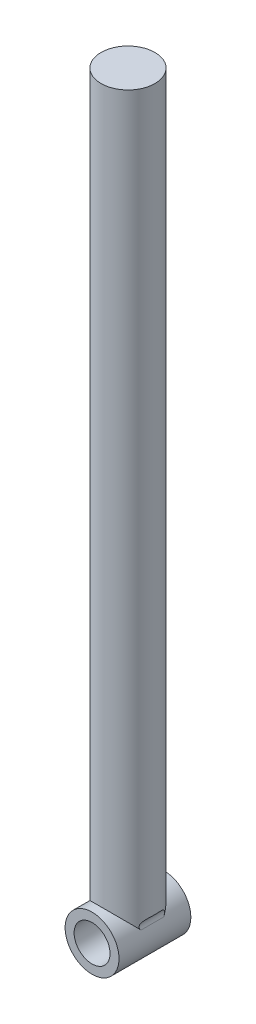
SolidWorks part; units mm, degrees
ref_plane "Front Plane" through (0, 0, 0) normal (0, 0, 1) x (1, 0, 0)
ref_plane "Top Plane" through (0, 0, 0) normal (0, 1, 0) x (1, 0, 0)
ref_plane "Right Plane" through (0, 0, 0) normal (1, 0, 0) x (0, 0, -1)
sketch "Sketch1" plane through (0, 0, 0) normal (0, 0, 1) x (1, 0, 0)
  circle A0 centre (0, 0) radius 25
  circle A1 centre (0, 0) radius 37.5
  dimension "D1" = 50
  dimension "D2" = 75
extrude "Boss-Extrude1" add sketch "Sketch1" along normal blind 100
sketch "Sketch2" plane through (0, 0, 0) normal (0, 1, 0) x (1, 0, 0)
  line L0 (0, 0) -> (0, -50) construction
  line L1 (37.5, 0) -> (-37.5, 0) construction
  line L2 (0, -50) -> (0, -100) construction
  line L3 (-37.5, -100) -> (37.5, -100) construction
  circle A0 centre (0, -50) radius 37.5
  dimension "D1" = 75
extrude "Boss-Extrude2" add sketch "Sketch2" along normal blind 1000 from offset 30
fillet "Fillet1" radius 10 2 edges at (22.5, 30, 50) (-22.5, 30, 50)
